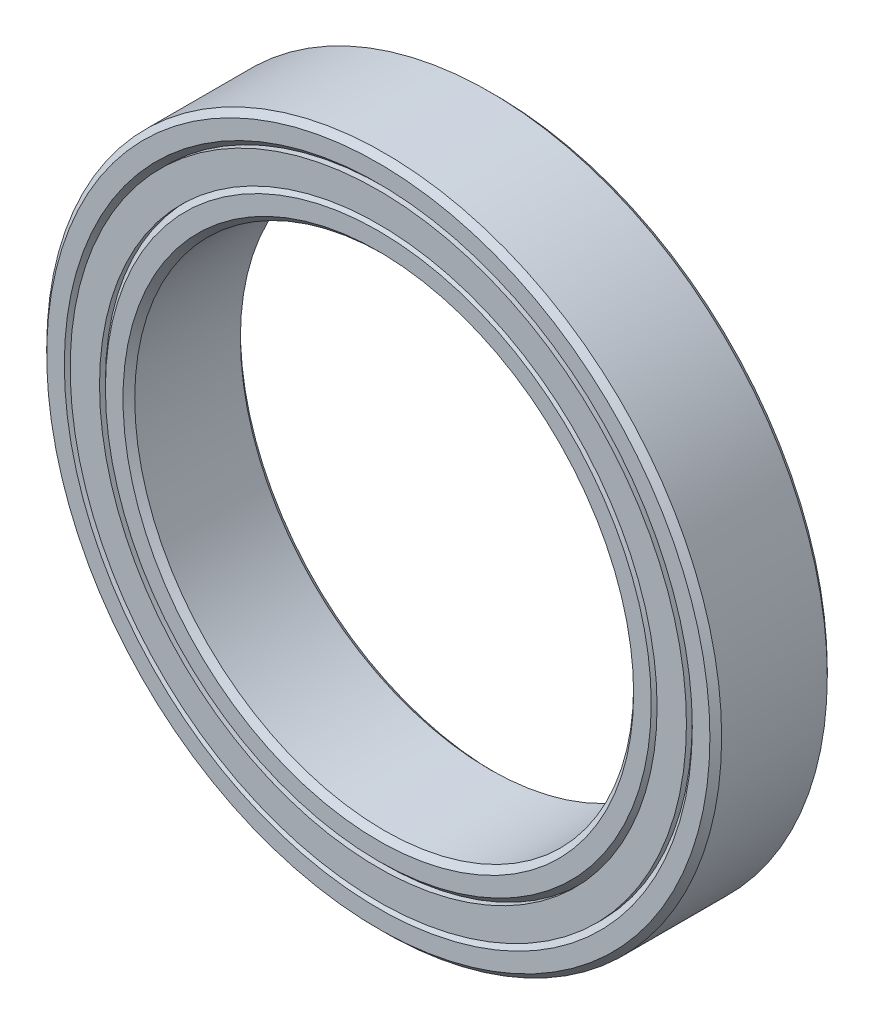
SolidWorks part; units mm, degrees
ref_plane "Front Plane" through (0, 0, 0) normal (0, 0, 1) x (1, 0, 0)
ref_plane "Top Plane" through (0, 0, 0) normal (0, 1, 0) x (1, 0, 0)
ref_plane "Right Plane" through (0, 0, 0) normal (1, 0, 0) x (0, 0, -1)
sketch "Sketch1" plane through (0, 0, 0) normal (0, 0, 1) x (1, 0, 0)
  circle A0 centre (0, 0) radius 8.5
  circle A1 centre (0, 0) radius 11.5
  circle A2 centre (0, 0) radius 9.5
  circle A3 centre (0, 0) radius 10.5
  dimension "D1" = 17
  dimension "D2" = 23
  dimension "D3" = 19
  dimension "D4" = 21
extrude "Boss-Extrude1" add sketch "Sketch1" along normal blind 4 contours A1 A3 | A2 A0 region at (-11.1747, 0, 0) region at (-9.2313, 0, 0)
chamfer "Chamfer1" distance 0.2 angle 45 4 edges at (11.5, 0, 0) (10.5, 0, 0) (10.5, 0, 4) (11.5, 0, 4)
chamfer "Chamfer2" distance 0.2 angle 45 4 edges at (8.5, 0, 0) (9.5, 0, 0) (8.5, 0, 4) (9.5, 0, 4)
extrude "Boss-Extrude2" add sketch "Sketch1<3>" along normal blind 4 contours A3 A2 region at (-10.203, 0, 0)
sketch "Sketch1<3>" plane through (0, 0, 0) normal (0, 0, 1) x (1, 0, 0) same geometry as "Sketch1"
